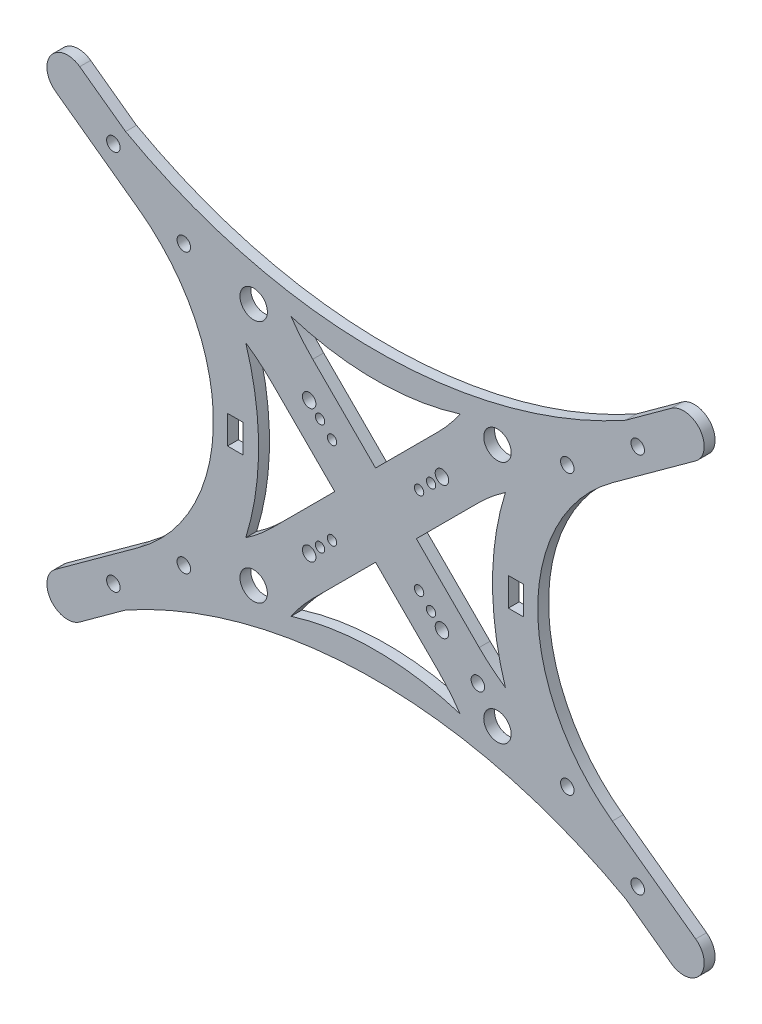
SolidWorks part; units mm, degrees
material "PPS"
ref_plane "前视基准面" through (0, 0, 0) normal (0, 0, 1) x (1, 0, 0)
ref_plane "上视基准面" through (0, 0, 0) normal (0, 1, 0) x (1, 0, 0)
ref_plane "右视基准面" through (0, 0, 0) normal (1, 0, 0) x (0, 0, -1)
sketch "草图7" plane through (0, 0, 0) normal (0, 0, 1) x (1, 0, 0)
  line L0 (-137.4469, 0) -> (193.7386, 0) construction
  line L1 (0, 90.5001) -> (0, -188.7446) construction
  line L2 (0, 0) -> (86.3378, -62.728) construction
  line L61 (-67.9485, -55.2388) -> (-57.4206, -47.5898)
  line L62 (-73.5325, -47.5531) -> (-54.395, -33.649)
  line L66 (-67.9485, 55.2388) -> (-57.4206, 47.5898)
  line L82 (-73.5325, 47.5531) -> (-54.395, 33.649)
  line L93 (73.5325, 47.5531) -> (54.395, 33.649)
  line L94 (-34, -3.25) -> (-34, 3.25) construction
  line L95 (67.9485, 55.2388) -> (57.4206, 47.5898)
  line L104 (15.25, 15.25) -> (0, 0) construction
  line L105 (67.9485, -55.2388) -> (57.4206, -47.5898)
  line L106 (73.5325, -47.5531) -> (54.395, -33.649)
  line L107 (0, 0) -> (86.3378, 62.728) construction
  circle A40 centre (10, 10) radius 1.075
  circle A65 centre (12.75, 12.75) radius 1.075
  circle A66 centre (15.25, 15.25) radius 1.55
  circle A73 centre (15.25, -15.25) radius 1.55
  circle A74 centre (12.75, -12.75) radius 1.075
  circle A75 centre (10, -10) radius 1.075
  circle A76 centre (28, -28) radius 3.15
  circle A89 centre (28, 28) radius 3.15
  arc A132 (67.9485, 55.2388) -> (73.5325, 47.5531) centre (70.7405, 51.396) cw
  arc A133 (54.395, 33.649) -> (54.395, -33.649) centre (78.8424, 0) ccw
  circle A134 centre (60.2246, 43.7557) radius 1.55
  arc A135 (-57.4206, -47.5898) -> (57.4206, -47.5898) centre (0, -151.3241) cw
  circle A136 centre (-60.2246, 43.7557) radius 1.55
  arc A138 (-54.395, 33.649) -> (-54.395, -33.649) centre (-78.8424, 0) cw
  arc A139 (-67.9485, 55.2388) -> (-73.5325, 47.5531) centre (-70.7405, 51.396) ccw
  circle A152 centre (-28, 28) radius 3.15
  circle A153 centre (-28, -28) radius 3.15
  circle A154 centre (-10, -10) radius 1.075
  circle A155 centre (-12.75, -12.75) radius 1.075
  circle A156 centre (-15.25, -15.25) radius 1.55
  circle A157 centre (-15.25, 15.25) radius 1.55
  circle A158 centre (-12.75, 12.75) radius 1.075
  circle A159 centre (-10, 10) radius 1.075
  arc A166 (-57.4206, 47.5898) -> (57.4206, 47.5898) centre (0, 151.3241) ccw
  arc A167 (67.9485, -55.2388) -> (73.5325, -47.5531) centre (70.7405, -51.396) ccw
  arc A172 (-67.9485, -55.2388) -> (-73.5325, -47.5531) centre (-70.7405, -51.396) cw
  circle A176 centre (60.2246, -43.7557) radius 1.55
  circle A177 centre (44.0442, -32) radius 1.55
  circle A178 centre (44.0442, 32) radius 1.55
  circle A179 centre (-44.0442, 32) radius 1.55
  circle A180 centre (-60.2246, -43.7557) radius 1.55
  circle A181 centre (-44.0442, -32) radius 1.55
  point P49 (-37.25, 0)
  dimension "D2" = 2.75
  dimension "D4" = 2.5
  dimension "D1" = 2.15
  dimension "D3" = 3.1
  dimension "D6" = 3.1
  dimension "D10" = 10
  dimension "D5" = 45
  dimension "D7" = 4.75
  dimension "D8" = 3.25
  dimension "D9" = 10
  dimension "D11" = 12.75
  dimension "D16" = 36
sketch "草图8" plane through (0, 0, 0) normal (0, 0, 1) x (1, 0, 0)
  line L0 (-96.7808, 0) -> (86.8563, 0) construction
  line L1 (0, 52.226) -> (0, -62.4511) construction
  line L2 (34, -3.25) -> (30.5, -3.25)
  line L3 (-34, 3.25) -> (-30.5, 3.25)
  line L4 (-34, 3.25) -> (-34, -3.25)
  line L5 (-34, -3.25) -> (-30.5, -3.25)
  line L6 (-30.5, 3.25) -> (-30.5, -3.25)
  line L7 (30.5, 3.25) -> (30.5, -3.25)
  line L8 (34, 3.25) -> (30.5, 3.25)
  line L9 (34, 3.25) -> (34, -3.25)
  dimension "D1" = 30.5
  dimension "D2" = 6.5
  dimension "D3" = 3.5
sketch "草图6" plane through (0, 0, 0) normal (0, 0, 1) x (1, 0, 0)
  line L3 (-23.8014, 14.4296) -> (-9.3719, 0)
  line L9 (-58.8867, 0) -> (57.6096, 0) construction
  line L14 (-23.8014, -14.4296) -> (-9.3719, 0)
  line L15 (0, 29.8455) -> (0, -115.5328) construction
  line L29 (14.4296, 23.8014) -> (0, 9.3719)
  line L30 (-14.4296, 23.8014) -> (0, 9.3719)
  line L31 (23.8014, -14.4296) -> (9.3719, 0)
  line L32 (23.8014, 14.4296) -> (9.3719, 0)
  line L33 (-14.4296, -23.8014) -> (0, -9.3719)
  line L34 (14.4296, -23.8014) -> (0, -9.3719)
  arc A18 (-23.8014, 14.4296) -> (-29.8202, 19.4008) centre (-52.8883, -14.6573) ccw
  arc A19 (-23.8014, -14.4296) -> (-29.8202, -19.4008) centre (-52.8883, 14.6573) cw
  arc A20 (-29.8202, -19.4008) -> (-29.8202, 19.4008) centre (-91.9966, 0) ccw
  arc A33 (-14.4296, 23.8014) -> (-19.4008, 29.8202) centre (14.6573, 52.8883) cw
  arc A34 (-19.4008, 29.8202) -> (19.4008, 29.8202) centre (0, 91.9966) ccw
  arc A35 (14.4296, 23.8014) -> (19.4008, 29.8202) centre (-14.6573, 52.8883) ccw
  arc A36 (23.8014, 14.4296) -> (29.8202, 19.4008) centre (52.8883, -14.6573) cw
  arc A37 (29.8202, 19.4008) -> (29.8202, -19.4008) centre (91.9966, 0) ccw
  arc A38 (23.8014, -14.4296) -> (29.8202, -19.4008) centre (52.8883, 14.6573) ccw
  arc A39 (14.4296, -23.8014) -> (19.4008, -29.8202) centre (-14.6573, -52.8883) cw
  arc A40 (19.4008, -29.8202) -> (-19.4008, -29.8202) centre (0, -91.9966) ccw
  arc A41 (-14.4296, -23.8014) -> (-19.4008, -29.8202) centre (14.6573, -52.8883) ccw
  point P49 (0, 0)
  dimension "D1" = 4
extrude "主结构-厚度还是得2.5, 不然铝柱不好选" add sketch "草图7" along normal blind 2.5
extrude "切除-拉伸2" cut sketch "草图6" along normal through all
extrude "切除-拉伸3" cut sketch "草图8" along normal through all
sketch "计算机板和PCB结构" plane through (0, 0, 0) normal (0, 0, 1) x (1, 0, 0)
  line L5 (0, 0) -> (0, 133.3353) construction
  line L6 (0, 0) -> (133.1914, 0) construction
  circle A0 centre (23.5, -21.7128) radius 1.55
  circle A2 centre (-29.25, 40.5) radius 1.55
  circle A4 centre (-17.5, -47.5) radius 1.55
  circle A6 centre (29.25, 40.5) radius 1.55
  circle A7 centre (17.5, -47.5) radius 1.55
  circle A8 centre (29.25, 40.5) radius 1.55
  dimension "D3" = 3.1
  dimension "D9" = 40.5
  dimension "D12" = 3.1
  dimension "D8" = 29.25
  dimension "D10" = 47.5
  dimension "D11" = 17.5
extrude "计算机板孔位和PCB孔位" cut sketch "计算机板和PCB结构" along normal through all contours A0 | A2 | A6 | A4 | A7 region at (23.5, -21.7128, 0) region at (-29.25, 40.5, 0) region at (-17.5, -47.5, 0) region at (29.25, 40.5, 0) region at (17.5, -47.5, 0)
